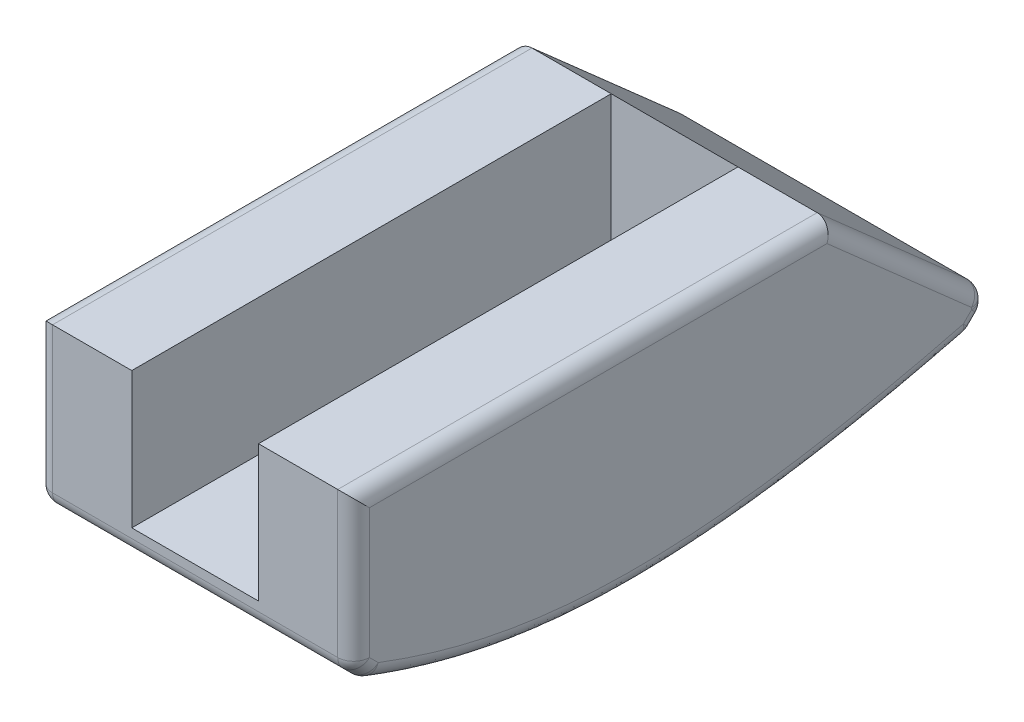
SolidWorks part; units mm, degrees
ref_plane "Front Plane" through (0, 0, 0) normal (0, 0, 1) x (1, 0, 0)
ref_plane "Top Plane" through (0, 0, 0) normal (0, 1, 0) x (1, 0, 0)
ref_plane "Right Plane" through (0, 0, 0) normal (1, 0, 0) x (0, 0, -1)
sketch "Sketch1" plane through (0, 0, 0) normal (1, 0, 0) x (0, 0, -1)
  line L1 (-37.8244, 21.5) -> (37.8244, 21.5) construction
  line L2 (-37.8244, 21.5) -> (-37.8244, 0) construction
  line L3 (-37.8244, 0) -> (37.8244, 0) construction
  line L4 (37.8244, 21.5) -> (37.8244, 0) construction
  dimension "D1" = 21.5
  dimension "D2" = 75.6488
sketch "Sketch4" plane through (0, 0, 0) normal (0, 1, 0) x (1, 0, 0)
  line L1 (-10, -37.8244) -> (10, -37.8244)
  line L2 (-10, -37.8244) -> (-10, 37.8244)
  line L3 (-10, 37.8244) -> (10, 37.8244)
  line L4 (10, -37.8244) -> (10, 37.8244)
  dimension "D1" = 20
sketch "Sketch5" plane through (0, 0, 0) normal (1, 0, 0) x (0, 0, -1)
  line L0 (-37.8244, 0) -> (-37.8244, -2.5)
  line L1 (62.1756, 0) -> (62.1756, -2.5)
  line L2 (62.1756, 0) -> (37.8244, 21.5)
  line L3 (37.8244, 21.5) -> (-37.8244, 21.5)
  line L4 (-37.8244, 21.5) -> (-37.8244, 0)
  line L5 (37.8244, 21.5) -> (37.8244, 0) construction
  line L6 (62.1756, -2.5) -> (-37.8244, -2.5) construction
  line L7 (59.6756, -5) -> (-35.3244, -5) construction
  line L8 (37.8244, 0) -> (62.1756, 0) construction
  line L9 (62.1756, -2.5) -> (59.6756, -5)
  line L10 (-37.8244, -2.5) -> (-35.3244, -5)
  spline S0 degree 3 poles (-35.3244, -5) (-13.5326, -13.3728) (11.7952, -17.2505) (59.6756, -5) knots 0 0 0 0 1 1 1 1
  dimension "D1" = 5
  dimension "D2" = 100
  dimension "D3" = 2.5
  dimension "D4" = 2.5
  dimension "D5" = 2.5
extrude "Boss-Extrude4" add sketch "Sketch5" along normal blind 25 and the other way blind 25
extrude "Cut-Extrude1" cut sketch "Sketch4" along normal through all
fillet "Fillet1" radius 2.5 19 edges at (-25, -1.25, -62.1756) (25, -1.25, -62.1756) (0, 0, -62.1756) (-25, -3.75, -60.9256) (25, -3.75, -60.9256) (0, -2.5, -62.1756) (0, -5, 35.3244) (0, -5, -59.6756) (25, -3.75, 36.5744) (-25, -3.75, 36.5744) (0, -2.5, 37.8244) (25, 9.5, 37.8244) (-25, 9.5, 37.8244) (25, 10.75, -50) (-25, 10.75, -50) (25, 21.5, 0) (-25, 21.5, 0)
